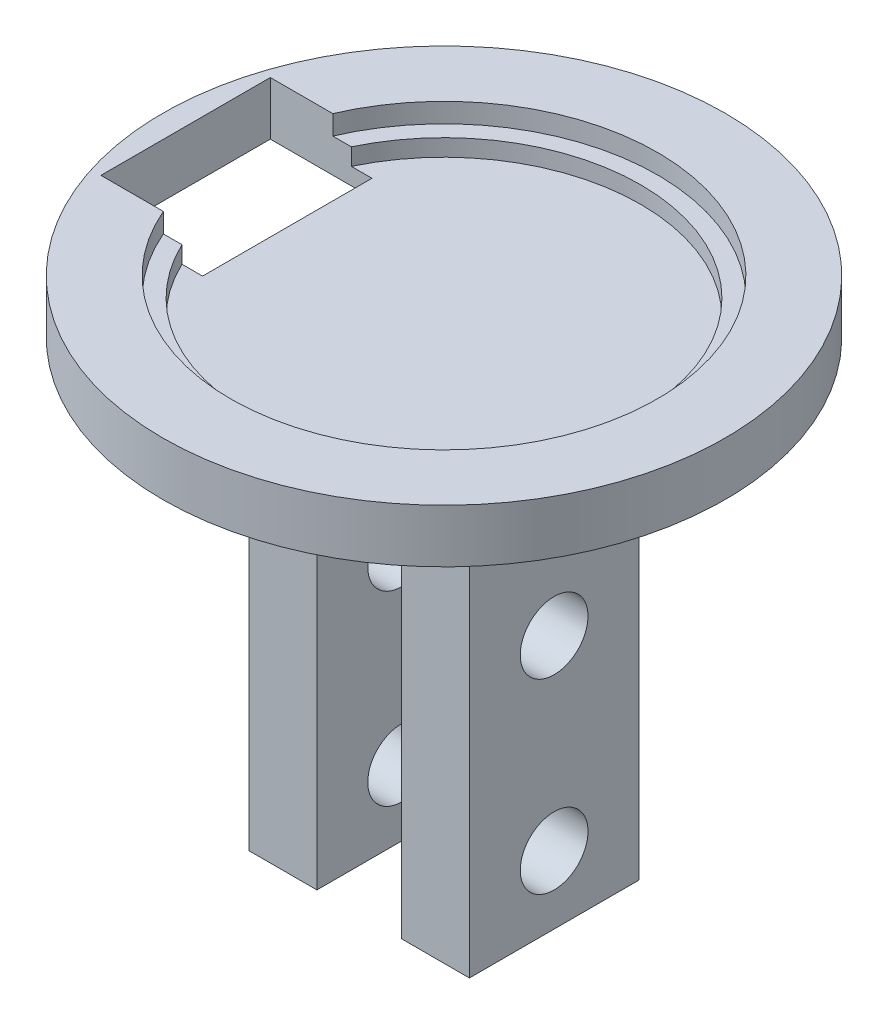
SolidWorks part; units mm, degrees
ref_plane "Front Plane" through (0, 0, 0) normal (0, 0, 1) x (1, 0, 0)
ref_plane "Top Plane" through (0, 0, 0) normal (0, 1, 0) x (1, 0, 0)
ref_plane "Right Plane" through (0, 0, 0) normal (1, 0, 0) x (0, 0, -1)
sketch "Sketch1" plane through (0, 0, 0) normal (0, 0, 1) x (1, 0, 0)
  line L0 (-14.45, -3.342) -> (-10.45, -3.342)
  line L1 (-10.45, -3.342) -> (-10.45, -4.492)
  line L2 (-10.45, -4.492) -> (-9.45, -4.492)
  line L3 (-9.45, -4.492) -> (-9.45, -5.492)
  line L4 (-9.45, -5.492) -> (2.15, -5.492)
  line L5 (-14.45, -3.342) -> (-14.45, -6.492)
  line L6 (-14.45, -6.492) -> (2.15, -6.492)
  line L7 (2.15, -6.492) -> (2.15, -5.492)
  dimension "D1" = 11.6
  dimension "D2" = 1
  dimension "D3" = 1
  dimension "D4" = 1
  dimension "D5" = 1.15
  dimension "D6" = 4
revolve "Revolve1" add sketch "Sketch1" angle 360 about L7
sketch "Sketch2" plane through (0, -6.492, 0) normal (0, -1, 0) x (1, 0, 0)
  line L0 (2.15, 16.6) -> (2.15, -16.6) construction
  line L1 (-14.45, 0) -> (18.75, 0) construction
  line L2 (8.65, -5) -> (4.65, -5)
  line L3 (-4.35, 5) -> (-0.35, 5)
  line L4 (-4.35, 5) -> (-4.35, -5)
  line L5 (-4.35, -5) -> (-0.35, -5)
  line L6 (-0.35, 5) -> (-0.35, -5)
  line L7 (-4.35, 5) -> (-0.35, -5) construction
  line L8 (-4.35, -5) -> (-0.35, 5) construction
  line L9 (4.65, 5) -> (4.65, -5)
  line L10 (8.65, 5) -> (4.65, 5)
  line L11 (8.65, 5) -> (8.65, -5)
  circle A0 centre (2.15, 0) radius 16.6 construction
  point P11 (-2.35, 0)
  dimension "D1" = 4
  dimension "D2" = 10
  dimension "D3" = 5
extrude "Boss-Extrude1" add sketch "Sketch2" along normal blind 27
sketch "Sketch3" plane through (-4.35, 0, 0) normal (-1, 0, 0) x (0, 0, 1)
  line L0 (0, -33.492) -> (0, -8.5072) construction
  line L1 (5, -33.492) -> (-5, -33.492) construction
  circle A0 centre (0, -29.492) radius 2
  circle A1 centre (0, -18.492) radius 2
  dimension "D1" = 4
  dimension "D2" = 4
  dimension "D3" = 4
  dimension "D4" = 11
extrude "Cut-Extrude1" cut sketch "Sketch3" against normal blind 22.3
fillet "Fillet1" radius 2.75 8 edges at (6.65, -6.492, -5) (-2.35, -6.492, -5) (6.65, -6.492, 5) (-2.35, -6.492, 5) (8.65, -6.492, 0) (4.65, -6.492, 0) (-0.35, -6.492, 0) (-4.35, -6.492, 0)
sketch "Sketch6" plane through (0, -6.492, 0) normal (0, -1, 0) x (1, 0, 0)
  line L0 (-7.1, 0) -> (-15.9092, 0) construction
  line L1 (-13.1, -5) -> (-7.1, -5)
  line L2 (-13.1, -5) -> (-13.1, 5)
  line L3 (-13.1, 5) -> (-7.1, 5)
  line L4 (-7.1, -5) -> (-7.1, 5)
  line L5 (-13.1, -5) -> (-7.1, 5) construction
  line L6 (-13.1, 5) -> (-7.1, -5) construction
  line L7 (-7.1, -7.75) -> (-7.1, 7.75) construction
  point P0 (-10.1, 0)
  dimension "D3" = 3
  dimension "D1" = 6
  dimension "D2" = 10
extrude "Cut-Extrude4" cut sketch "Sketch6" against normal blind 10
